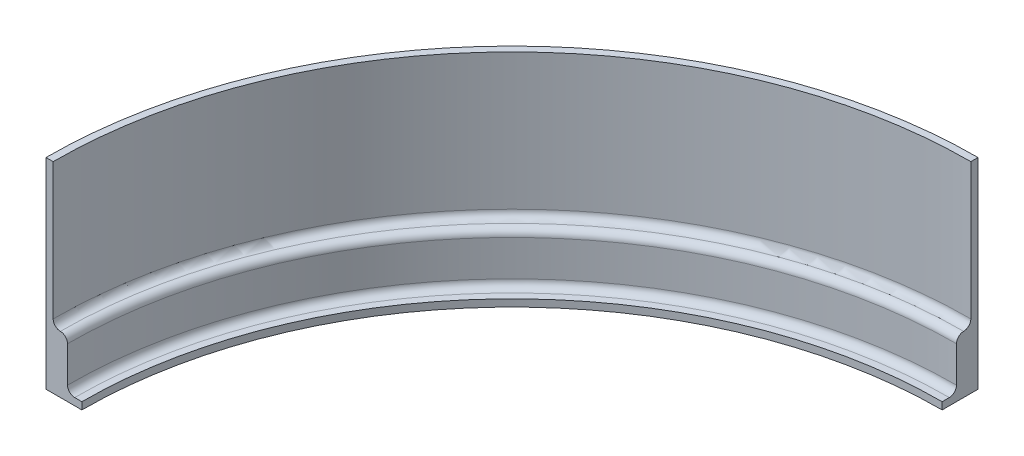
SolidWorks part; units mm, degrees
material "AISI 4340 Steel, annealed"
ref_plane "Front Plane" through (0, 0, 0) normal (0, 0, 1) x (1, 0, 0)
ref_plane "Top Plane" through (0, 0, 0) normal (0, 1, 0) x (1, 0, 0)
ref_plane "Right Plane" through (0, 0, 0) normal (1, 0, 0) x (0, 0, -1)
sketch "Sketch1" plane through (0, 0, 0) normal (0, 1, 0) x (1, 0, 0)
  line L0 (300, 300) -> (300, 325)
  line L1 (-25, 0) -> (0, 0)
  arc A0 (0, 0) -> (300, 300) centre (300, 0) cw
  arc A1 (300, 325) -> (-25, 0) centre (300, 0) ccw
  dimension "D1" = 300
  dimension "D2" = 25
extrude "Bottom level" add sketch "Sketch1" along normal blind 5
sketch "Sketch2" plane through (0, 5, 0) normal (0, 1, 0) x (1, 0, 0)
  line L0 (-25, 0) -> (-10, 0)
  line L1 (300, 325) -> (300, 310)
  arc A0 (300, 325) -> (-25, 0) centre (300, 0) ccw construction
  arc A1 (300, 325) -> (-25, 0) centre (300, 0) ccw
  arc A2 (300, 310) -> (-10, 0) centre (300, 0) ccw
  dimension "D1" = 15
extrude "Mid level" add sketch "Sketch2" along normal blind 35
sketch "Sketch3" plane through (0, 40, 0) normal (0, 1, 0) x (1, 0, 0)
  line L0 (-25, 0) -> (-20, 0)
  line L1 (300, 325) -> (300, 320)
  arc A0 (300, 325) -> (-25, 0) centre (300, 0) ccw construction
  arc A1 (300, 325) -> (-25, 0) centre (300, 0) ccw
  arc A2 (300, 320) -> (-20, 0) centre (300, 0) ccw
  dimension "D1" = 5
extrude "Guard rail" add sketch "Sketch3" along normal blind 100
fillet "Rounding" radius 5 3 edges at (80.7969, 5, -219.2031) (80.7969, 40, -219.2031) (73.7258, 40, -226.2742)
